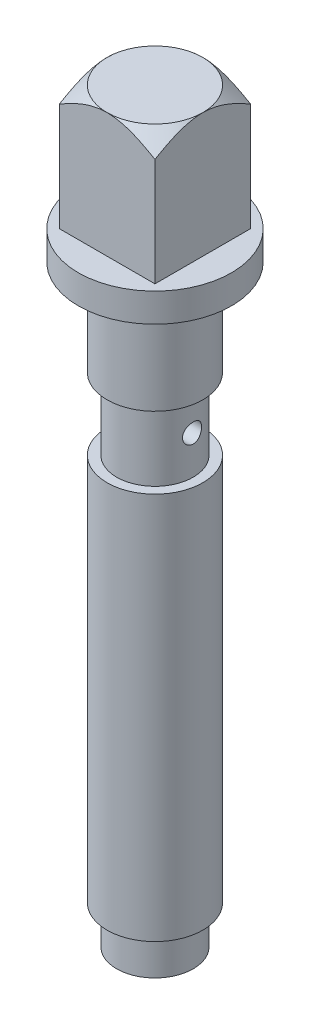
SolidWorks part; units mm, degrees
ref_plane "Front Plane" through (0, 0, 0) normal (0, 0, 1) x (1, 0, 0)
ref_plane "Top Plane" through (0, 0, 0) normal (0, 1, 0) x (1, 0, 0)
ref_plane "Right Plane" through (0, 0, 0) normal (1, 0, 0) x (0, 0, -1)
sketch "Sketch2" plane through (0, 0, 0) normal (0, 1, 0) x (1, 0, 0)
  circle A0 centre (0, 0) radius 4
  dimension "D1" = 8
extrude "Boss-Extrude1" add sketch "Sketch2" along normal blind 4
sketch "Sketch3" plane through (0, 4, 0) normal (0, 1, 0) x (1, 0, 0)
  circle A0 centre (0, 0) radius 5
  dimension "D1" = 10
extrude "Boss-Extrude2" add sketch "Sketch3" along normal blind 40.5
cosmetic thread "Cosmetic Thread1" parameters "D2"=8.344
sketch "Sketch4" plane through (0, 44.5, 0) normal (0, 1, 0) x (1, 0, 0)
  circle A0 centre (0, 0) radius 4
  dimension "D1" = 8
extrude "Boss-Extrude3" add sketch "Sketch4" along normal blind 7.5
sketch "Sketch5" plane through (0, 0, 0) normal (1, 0, 0) x (0, 0, -1)
  line L0 (5, 44.5) -> (-5, 44.5) construction
  circle A0 centre (0, 48.5) radius 1
  dimension "D1" = 2
  dimension "D2" = 4
extrude "Cut-Extrude1" cut sketch "Sketch5" against normal blind 7.5 and the other way blind 7.5
sketch "Sketch6" plane through (0, 52, 0) normal (0, 1, 0) x (1, 0, 0)
  circle A0 centre (0, 0) radius 5
  dimension "D1" = 10
extrude "Boss-Extrude4" add sketch "Sketch6" along normal blind 10
sketch "Sketch7" plane through (0, 62, 0) normal (0, 1, 0) x (1, 0, 0)
  circle A0 centre (0, 0) radius 8
  dimension "D1" = 16
extrude "Boss-Extrude5" add sketch "Sketch7" along normal blind 3
sketch "Sketch8" plane through (0, 65, 0) normal (0, 1, 0) x (1, 0, 0)
  line L1 (-5, 5) -> (5, 5)
  line L2 (-5, 5) -> (-5, -5)
  line L3 (-5, -5) -> (5, -5)
  line L4 (5, 5) -> (5, -5)
  line L5 (-5, 5) -> (5, -5) construction
  line L6 (-5, -5) -> (5, 5) construction
  point P0 (0, 0)
  dimension "D1" = 10
  dimension "D2" = 10
extrude "Boss-Extrude6" add sketch "Sketch8" along normal blind 13
sketch "Sketch9" plane through (0, 78, 0) normal (0, 1, 0) x (1, 0, 0)
  line L0 (-5, -5) -> (5, -5) construction
  line L1 (-5, 5) -> (-5, -5) construction
  line L2 (5, 5) -> (-5, 5) construction
  line L3 (5, -5) -> (5, 5) construction
  circle A0 centre (0, 0) radius 5
extrude "Cut-Extrude3" cut sketch "Sketch9" against normal blind 2 draft 50 flip side to cut
